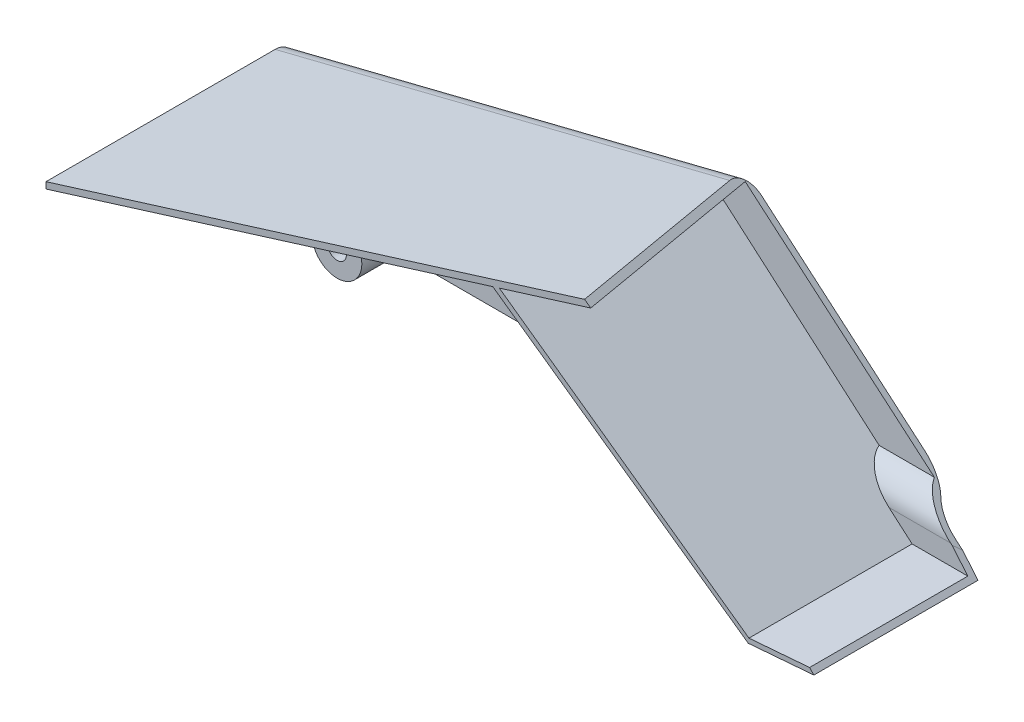
SolidWorks part; units mm, degrees
ref_plane "Piano frontale" through (0, 0, 0) normal (0, 0, 1) x (1, 0, 0)
ref_plane "Piano superiore" through (0, 0, 0) normal (0, 1, 0) x (1, 0, 0)
ref_plane "Piano destro" through (0, 0, 0) normal (1, 0, 0) x (0, 0, -1)
sketch "Schizzo1" plane through (0, 0, 0) normal (0, 0, 1) x (1, 0, 0)
  line L0 (-49, 0) -> (49, 0)
  line L1 (-49, 0) -> (-49, 5)
  line L2 (-49, 5) -> (-65, 5)
  line L3 (-65, 5) -> (-65, 17)
  line L4 (-65, 17) -> (17.4553, 37.6429)
  line L5 (17.4553, 37.6429) -> (49, 0)
  point P4 (0, 0)
  point P8 (2.9043, 34)
  dimension "D1" = 98
  dimension "D2" = 5
  dimension "D3" = 16
  dimension "D4" = 12
  dimension "D5" = 85
  dimension "D6" = 70
  dimension "D7" = 34
extrude "Estrusione-Estrusione1" add sketch "Schizzo1" along normal blind 40
sketch "Schizzo3" plane through (0, 0, 0) normal (1, 0, 0) x (0, 0, -1)
  line L0 (-3.5, 4) -> (-3.5, 0)
  line L1 (-40, 0) -> (0, 0) construction
  line L2 (-3.5, 0) -> (0, 0)
  line L3 (0, 0) -> (0, 0.5)
  line L4 (0, 0.5) -> (0, 7.5)
  arc A0 (0, 7.5) -> (-3.5, 4) centre (0, 4) ccw
  dimension "D1" = 7
  dimension "D2" = 4
extrude "Taglio-Estrusione1" cut sketch "Schizzo3" against normal through all both and the other way through all
shell "Svuota1" thickness 1 removed face at (0, 0, 21.75) removed face at (-49, 2.8011, 18.0781) removed face at (-57, 5, 21.6771) removed face at (-65, 10.4112, 16.7537) removed face at (-26.9241, 10.7738, 40) removed face at (36.7777, 14.5851, 14.6208)
sketch "Schizzo5" plane through (0, 0, 0) normal (0, 0, 1) x (1, 0, 0)
  line L0 (1.3224, 32.5731) -> (2.2925, 32.816)
  line L1 (18.1693, 36.7908) -> (-65, 15.9691) construction
  line L2 (2.2925, 32.816) -> (39.3577, 0.7665)
  line L3 (39.3577, 0.7665) -> (48.3577, 0.7665)
  line L4 (49, 0) -> (45.648, 4) construction
  line L5 (48.3577, 0.7665) -> (49, 0)
  line L6 (49, 0) -> (39.2565, 0)
  line L7 (-49, 0) -> (49, 0) construction
  line L8 (39.2565, 0) -> (1.3224, 32.5731)
  dimension "D1" = 1
  dimension "D2" = 1
  dimension "D3" = 49
  dimension "D4" = 50
  dimension "D5" = 9
extrude "Estrusione-Estrusione2" add sketch "Schizzo5" against normal up to body from surface separate body starting at face at (-23.5938, 26.8507, 40)
sketch "Schizzo8" plane through (0, 0, 0) normal (0, 0, 1) x (1, 0, 0)
  line L0 (-49, 4) -> (-49, 0) construction
  line L1 (-49, 0) -> (39.2565, 0) construction
  circle A0 centre (-45, 4) radius 4
  circle A1 centre (9, 4) radius 4
  dimension "D1" = 8
  dimension "D2" = 54
extrude "Estrusione-Estrusione3" add sketch "Schizzo8" against normal up to body from offset 13 separate body
sketch "Schizzo9" plane through (0, 0, 0) normal (0, 0, 1) x (1, 0, 0)
  circle A0 centre (-45, 4) radius 1.5
  circle A1 centre (9, 4) radius 1.5
  arc A2 (-49, 4) -> (-45, 0) centre (-45, 4) ccw construction
  dimension "D1" = 3
extrude "Taglio-Estrusione2" cut sketch "Schizzo9" against normal blind 30 from surface starting at face at (-41, 4, 13)
ref_plane "Piano1" through (-7.8386, 31.3105, 0) normal (-0.2429, 0.9701, 0) x (0.9701, 0.2429, 0)
sketch "Schizzo13" plane through (-7.8386, 31.3105, 0) normal (-0.2429, 0.9701, 0) x (0.9701, 0.2429, 0)
  line L1 (26.0745, 0) -> (-58.9255, 0) construction
  line L2 (16.0745, 0) -> (26.0745, 0)
  line L3 (26.0745, 0) -> (26.0745, -40)
  line L4 (26.0745, -40) -> (25.0745, -40)
  line L5 (26.0745, -40) -> (-58.9255, -40) construction
  line L6 (25.0745, -40) -> (16.0745, 0)
  dimension "D1" = 10
  dimension "D2" = 1
sketch "Schizzo17" plane through (0, 0, 0) normal (0, 0, 1) x (1, 0, 0)
  line L0 (7.7547, 35.2143) -> (60.9911, -10.2377)
  line L8 (17.4553, 37.6429) -> (-65, 17) construction
  dimension "D1" = 10
  dimension "D2" = 70
sweep "Taglia-Sweep3" cut profiles "Schizzo13" path "Schizzo17"
sketch "Schizzo18" plane through (0, 0, 0) normal (0, 1, 0) x (1, 0, 0)
  line L1 (-1, -3) -> (-12, -3)
  line L2 (-1, -3) -> (-1, -4)
  line L3 (-1, -4) -> (-12, -4)
  line L4 (-12, -3) -> (-12, -4)
  line L5 (5, -4.5) -> (5, -13) construction
  line L6 (-45, -4.5) -> (9, -4.5) construction
  point P6 (-1, -3.5)
  dimension "D1" = 1
  dimension "D2" = 11
  dimension "D3" = 6
  dimension "D4" = 0.5
extrude "Taglio-Estrusione3" cut sketch "Schizzo18" along normal blind 5
fillet "Raccordo1" radius 2 1 edges at (16.952, 37.0014, 40) type face fillet first side face at (31.2304, 17.569, 9.9493) second side face at (8.3491, 17.3894, 40)
fillet "Raccordo2" radius 3 1 edges at (-28.6227, 26.1071, 0) type face fillet first side face at (-18.398, 28.6669, 23.62) second side face at (-20.5075, 16.8036, 0)
fillet "Raccordo3" radius 4 1 edges at (-12.3923, 7.5, 0)
sketch "Schizzo22" plane through (0, 0, 0) normal (0, 1, 0) x (1, 0, 0)
  line L0 (-65, -40) -> (49, -30)
  line L1 (49, -40) -> (49, -3.5) construction
  line L2 (49, -30) -> (49, -40)
  line L4 (13.6272, -40) -> (49, -40)
  line L5 (13.6272, -40) -> (-65, -40) construction
  line L6 (13.6272, -40) -> (-65, -40)
  dimension "D2" = 10
extrude "Taglio-Estrusione4" cut sketch "Schizzo22" against normal blind 10 and the other way through all
